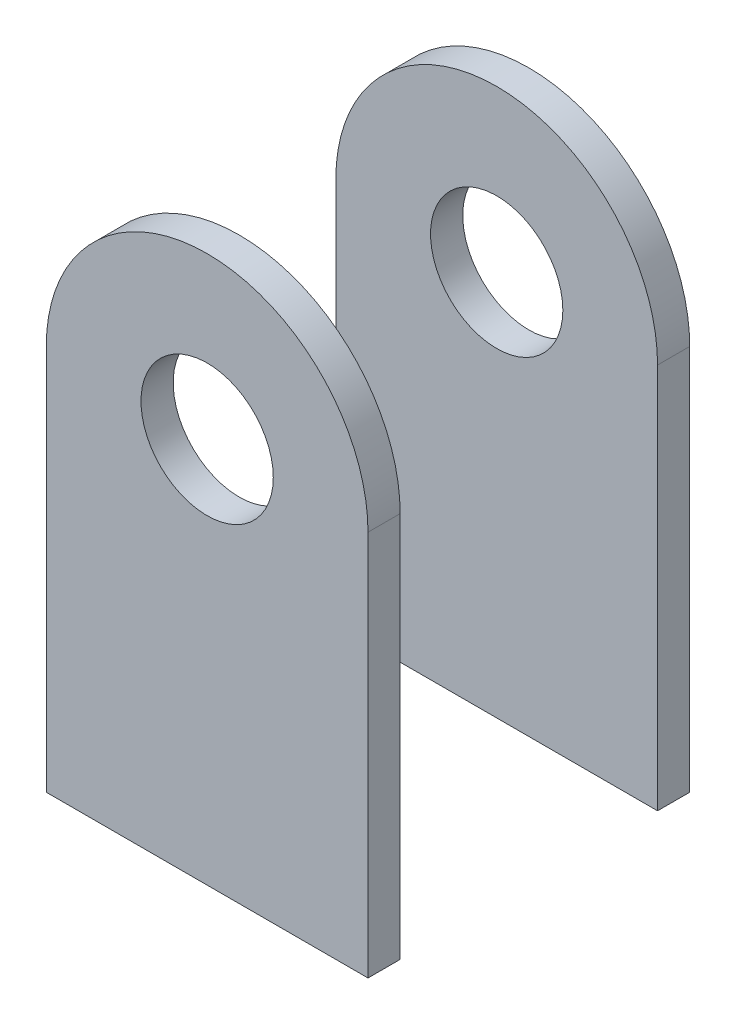
SolidWorks part; units mm, degrees
material "AISI 4130 Steel, normalized at 870C"
ref_plane "Front Plane" through (0, 0, 0) normal (0, 0, 1) x (1, 0, 0)
ref_plane "Top Plane" through (0, 0, 0) normal (0, 1, 0) x (1, 0, 0)
ref_plane "Right Plane" through (0, 0, 0) normal (1, 0, 0) x (0, 0, -1)
sketch "Sketch1" plane through (0, 0, 0) normal (0, 0, 1) x (1, 0, 0)
  line L0 (7.9375, 0) -> (7.9375, -19.05)
  line L1 (7.9375, -19.05) -> (-7.9375, -19.05)
  line L2 (-7.9375, -19.05) -> (-7.9375, 0)
  line L3 (0, 0) -> (0, -19.05) construction
  circle A0 centre (0, 0) radius 3.2639
  circle A1 centre (0, 0) radius 7.9375
  dimension "D1" = 6.5278
  dimension "D2" = 15.875
  dimension "D3" = 19.05
extrude "Boss-Extrude1" add sketch "Sketch1" along normal blind 1.5875 from offset 6.35 contours A1 A0 | A1 L2 L1 L0 | L3 A1 L2 L1 region at (5.4539, -5.4539, 0) region at (4.2606, -12.5196, 0) region at (-4.2606, -12.5196, 0)
extrude "Boss-Extrude2" add sketch "Sketch1<4>" against normal blind 1.5875 from offset 6.35 separate body contours A1 A0 | A1 L2 L1 L0 | L3 A1 L2 L1 region at (5.4539, -5.4539, 0) region at (4.2606, -12.5196, 0) region at (-4.2606, -12.5196, 0) offset against normal yes
sketch "Sketch1<4>" plane through (0, 0, 0) normal (0, 0, 1) x (1, 0, 0) same geometry as "Sketch1"
equation "\"Width Between Tabs\"= .5"
equation "\"Tab Thickness\"= 1 / 16"
equation "\"D19@Boss-Extrude1\"=\"Width Between Tabs\"/2"
equation "\"D1@Boss-Extrude1\"=\"Tab Thickness\""
equation "\"D19@Boss-Extrude2\"=\"Width Between Tabs\"/2"
equation "\"D1@Boss-Extrude2\"=\"Tab Thickness\""
equation "\"Hole Diameter\"= .257"
equation "\"D1@Sketch1\"=\"Hole Diameter\""
